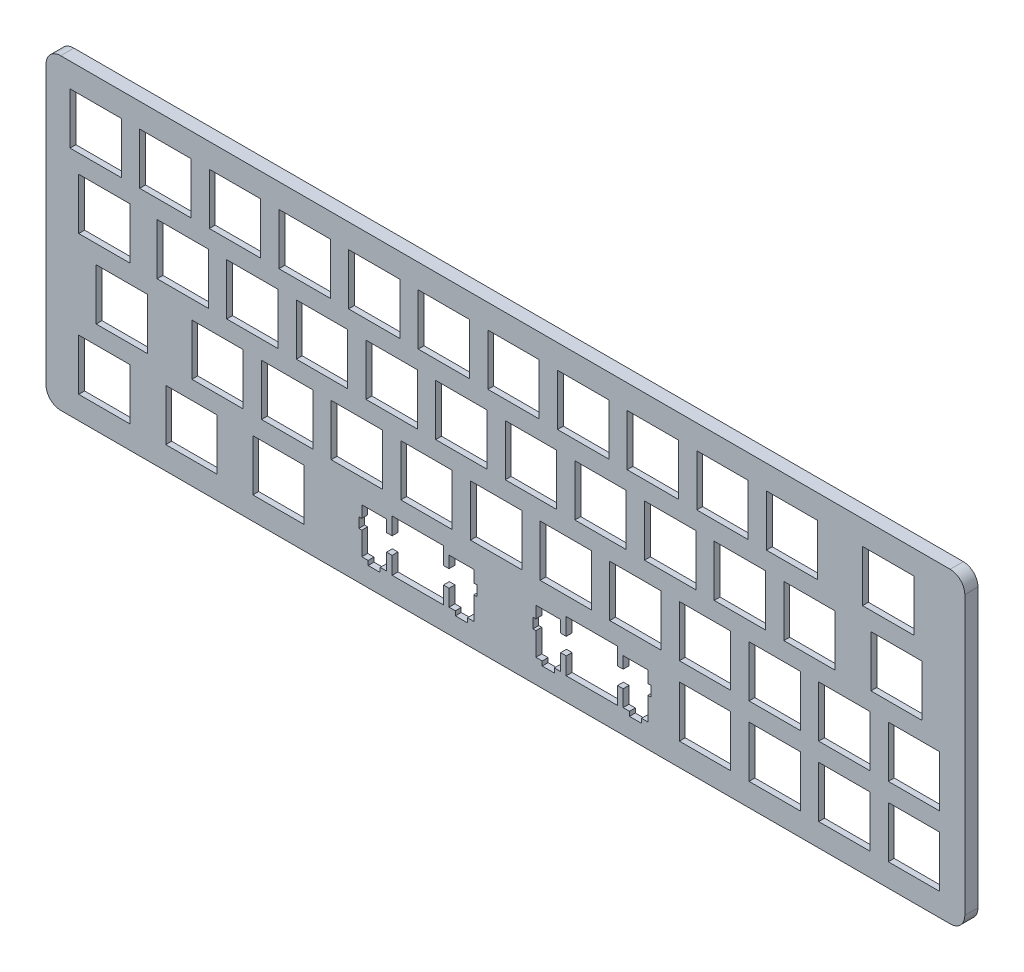
SolidWorks part; units mm, degrees
ref_plane "Front Plane" through (0, 0, 0) normal (0, 0, 1) x (1, 0, 0)
ref_plane "Top Plane" through (0, 0, 0) normal (0, 1, 0) x (1, 0, 0)
ref_plane "Right Plane" through (0, 0, 0) normal (1, 0, 0) x (0, 0, -1)
sketch "Sketch1" plane through (0, 0, 0) normal (0, 0, 1) x (1, 0, 0)
  line L0 (99.95, -108.45) -> (342.62, -108.45)
  line L1 (344.62, -110.45) -> (344.62, -186.25)
  line L2 (342.62, -188.25) -> (99.95, -188.25)
  line L3 (97.95, -186.25) -> (97.95, -110.45)
  line L4 (97.95, -110.45) -> (97.95, -186.25)
  line L5 (99.95, -106.45) -> (342.62, -106.45)
  line L6 (346.62, -110.45) -> (346.62, -186.25)
  line L7 (342.62, -190.25) -> (99.95, -190.25)
  line L8 (95.95, -110.45) -> (95.95, -186.25)
  circle A0 centre (147.5, -114.3) radius 1.1
  circle A1 centre (325.72, -114.3) radius 1.1
  circle A2 centre (332.75, -171.3) radius 1.1
  circle A3 centre (218.75, -152.3) radius 1.1138
  circle A4 centre (111.875, -171.3) radius 1.106
  arc A5 (342.62, -108.45) -> (344.62, -110.45) centre (342.62, -110.45) cw
  arc A6 (344.62, -186.25) -> (342.62, -188.25) centre (342.62, -186.25) cw
  arc A7 (99.95, -188.25) -> (97.95, -186.25) centre (99.95, -186.25) cw
  arc A8 (97.95, -110.45) -> (99.95, -108.45) centre (99.95, -110.45) cw
  arc A9 (95.95, -110.45) -> (99.95, -106.45) centre (99.95, -110.45) cw
  arc A10 (342.62, -106.45) -> (346.62, -110.45) centre (342.62, -110.45) cw
  arc A11 (346.62, -186.25) -> (342.62, -190.25) centre (342.62, -186.25) cw
  arc A12 (99.95, -190.25) -> (95.95, -186.25) centre (99.95, -186.25) cw
  dimension "D1" = 2
sketch "Sketch3" plane through (0, 0, 0) normal (0, 0, 1) x (1, 0, 0)
  line B0 (230.5, -113) -> (216.5, -113)
  line B1 (211.5, -127) -> (211.5, -113)
  line B2 (197.5, -113) -> (197.5, -127)
  line B3 (197.25, -132) -> (183.25, -132)
  line B4 (202.25, -146) -> (216.25, -146)
  line B5 (202.25, -132) -> (202.25, -146)
  line B6 (287.75, -170) -> (287.75, -184)
  line B7 (268.75, -165) -> (282.75, -165)
  line B8 (268.75, -151) -> (268.75, -165)
  line B9 (263.75, -151) -> (249.75, -151)
  line B10 (282.75, -151) -> (268.75, -151)
  line B11 (297.25, -146) -> (311.25, -146)
  line B12 (321, -146) -> (335, -146)
  line B13 (297.25, -132) -> (297.25, -146)
  line B14 (292.25, -146) -> (292.25, -132)
  line B15 (278.25, -132) -> (278.25, -146)
  line B16 (273.25, -146) -> (273.25, -132)
  line B17 (259.25, -132) -> (259.25, -146)
  line B18 (254.25, -146) -> (254.25, -132)
  line B19 (240.25, -146) -> (254.25, -146)
  line B20 (235.25, -132) -> (221.25, -132)
  line B21 (221.25, -146) -> (235.25, -146)
  line B22 (230.75, -165) -> (244.75, -165)
  line B23 (251.875, -170) -> (237.875, -170)
  line B24 (237.875, -170) -> (237.875, -184)
  line B25 (244.75, -165) -> (244.75, -151)
  line B26 (244.75, -151) -> (230.75, -151)
  line B27 (235.25, -146) -> (235.25, -132)
  line B28 (235.5, -113) -> (235.5, -127)
  line B29 (320.75, -184) -> (320.75, -170)
  line B30 (320.75, -170) -> (306.75, -170)
  line B31 (263.75, -165) -> (263.75, -151)
  line B32 (249.75, -151) -> (249.75, -165)
  line B33 (230.75, -151) -> (230.75, -165)
  line B34 (225.75, -165) -> (225.75, -151)
  line B35 (192.75, -151) -> (192.75, -165)
  line B36 (173.75, -165) -> (187.75, -165)
  line B37 (154.75, -165) -> (168.75, -165)
  line B38 (135.75, -165) -> (149.75, -165)
  line B39 (109.625, -165) -> (123.625, -165)
  line B40 (190.375, -184) -> (204.375, -184)
  line B41 (204.375, -184) -> (204.375, -170)
  line B42 (211.75, -151) -> (211.75, -165)
  line B43 (225.75, -151) -> (211.75, -151)
  line B44 (183.25, -146) -> (197.25, -146)
  line B45 (164.25, -132) -> (164.25, -146)
  line B46 (159.25, -146) -> (159.25, -132)
  line B47 (145.25, -132) -> (145.25, -146)
  line B48 (140.25, -146) -> (140.25, -132)
  line B49 (140.25, -132) -> (126.25, -132)
  line B50 (121.5, -127) -> (135.5, -127)
  line B51 (135.5, -113) -> (121.5, -113)
  line B52 (149.75, -151) -> (135.75, -151)
  line B53 (126.25, -146) -> (140.25, -146)
  line B54 (126.25, -132) -> (126.25, -146)
  line B55 (249.5, -127) -> (249.5, -113)
  line B56 (268.5, -127) -> (268.5, -113)
  line B57 (287.5, -113) -> (273.5, -113)
  line B58 (292.5, -113) -> (292.5, -127)
  line B59 (306.5, -127) -> (306.5, -113)
  line B60 (318.72, -127) -> (332.72, -127)
  line B61 (311.25, -146) -> (311.25, -132)
  line B62 (221.25, -132) -> (221.25, -146)
  line B63 (216.25, -146) -> (216.25, -132)
  line B64 (183.25, -132) -> (183.25, -146)
  line B65 (178.25, -146) -> (178.25, -132)
  line B66 (164.25, -146) -> (178.25, -146)
  line B67 (145.25, -146) -> (159.25, -146)
  line B68 (168.75, -151) -> (154.75, -151)
  line B69 (187.75, -151) -> (173.75, -151)
  line B70 (206.75, -165) -> (206.75, -151)
  line B71 (211.75, -165) -> (225.75, -165)
  line B72 (173.75, -151) -> (173.75, -165)
  line B73 (168.75, -165) -> (168.75, -151)
  line B74 (149.75, -165) -> (149.75, -151)
  line B75 (135.75, -151) -> (135.75, -165)
  line B76 (159.25, -132) -> (145.25, -132)
  line B77 (178.5, -113) -> (178.5, -127)
  line B78 (192.5, -113) -> (178.5, -113)
  line B79 (142.625, -170) -> (128.625, -170)
  line B80 (118.875, -184) -> (118.875, -170)
  line B81 (104.875, -170) -> (104.875, -184)
  line B82 (118.875, -170) -> (104.875, -170)
  line B83 (204.375, -170) -> (190.375, -170)
  line B84 (166.375, -184) -> (166.375, -170)
  line B85 (166.375, -170) -> (152.375, -170)
  line B86 (128.625, -170) -> (128.625, -184)
  line B87 (154.75, -151) -> (154.75, -165)
  line B88 (116.5, -127) -> (116.5, -113)
  line B89 (211.5, -113) -> (197.5, -113)
  line B90 (197.5, -127) -> (211.5, -127)
  line B91 (216.25, -132) -> (202.25, -132)
  line B92 (206.75, -151) -> (192.75, -151)
  line B93 (187.75, -165) -> (187.75, -151)
  line B94 (282.75, -184) -> (282.75, -170)
  line B95 (282.75, -170) -> (268.75, -170)
  line B96 (249.75, -165) -> (263.75, -165)
  line B97 (292.25, -132) -> (278.25, -132)
  line B98 (311.25, -132) -> (297.25, -132)
  line B99 (135.5, -127) -> (135.5, -113)
  line B100 (140.5, -113) -> (140.5, -127)
  line B101 (140.5, -127) -> (154.5, -127)
  line B102 (102.5, -113) -> (102.5, -127)
  line B103 (102.5, -127) -> (116.5, -127)
  line B104 (121.5, -113) -> (121.5, -127)
  line B105 (154.5, -113) -> (140.5, -113)
  line B106 (306.75, -184) -> (320.75, -184)
  line B107 (306.75, -170) -> (306.75, -184)
  line B108 (301.75, -184) -> (301.75, -170)
  line B109 (99.95, -106.45) -> (342.62, -106.45)
  line B110 (154.5, -127) -> (154.5, -113)
  line B111 (173.5, -113) -> (159.5, -113)
  line B112 (95.95, -186.25) -> (95.95, -110.45)
  line B113 (346.62, -110.45) -> (346.62, -186.25)
  line B114 (342.62, -190.25) -> (99.95, -190.25)
  line B115 (116.5, -113) -> (102.5, -113)
  line B116 (159.5, -127) -> (173.5, -127)
  line B117 (173.5, -127) -> (173.5, -113)
  line B118 (159.5, -113) -> (159.5, -127)
  line B119 (178.5, -127) -> (192.5, -127)
  line B120 (192.5, -127) -> (192.5, -113)
  line B121 (216.5, -127) -> (230.5, -127)
  line B122 (230.5, -127) -> (230.5, -113)
  line B123 (216.5, -113) -> (216.5, -127)
  line B124 (235.5, -127) -> (249.5, -127)
  line B125 (249.5, -113) -> (235.5, -113)
  line B126 (254.5, -127) -> (268.5, -127)
  line B127 (268.5, -113) -> (254.5, -113)
  line B128 (254.5, -113) -> (254.5, -127)
  line B129 (273.5, -127) -> (287.5, -127)
  line B130 (287.5, -127) -> (287.5, -113)
  line B131 (273.5, -113) -> (273.5, -127)
  line B132 (292.5, -127) -> (306.5, -127)
  line B133 (306.5, -113) -> (292.5, -113)
  line B134 (332.72, -127) -> (332.72, -113)
  line B135 (332.72, -113) -> (318.72, -113)
  line B136 (318.72, -113) -> (318.72, -127)
  line B137 (104.875, -146) -> (118.875, -146)
  line B138 (118.875, -146) -> (118.875, -132)
  line B139 (118.875, -132) -> (104.875, -132)
  line B140 (104.875, -132) -> (104.875, -146)
  line B141 (178.25, -132) -> (164.25, -132)
  line B142 (197.25, -146) -> (197.25, -132)
  line B143 (254.25, -132) -> (240.25, -132)
  line B144 (240.25, -132) -> (240.25, -146)
  line B145 (259.25, -146) -> (273.25, -146)
  line B146 (273.25, -132) -> (259.25, -132)
  line B147 (278.25, -146) -> (292.25, -146)
  line B148 (335, -146) -> (335, -132)
  line B149 (335, -132) -> (321, -132)
  line B150 (321, -132) -> (321, -146)
  line B151 (123.625, -165) -> (123.625, -151)
  line B152 (123.625, -151) -> (109.625, -151)
  line B153 (109.625, -151) -> (109.625, -165)
  line B154 (192.75, -165) -> (206.75, -165)
  line B155 (282.75, -165) -> (282.75, -151)
  line B156 (287.75, -165) -> (301.75, -165)
  line B157 (301.75, -165) -> (301.75, -151)
  line B158 (301.75, -151) -> (287.75, -151)
  line B159 (287.75, -151) -> (287.75, -165)
  line B160 (306.75, -165) -> (320.75, -165)
  line B161 (320.75, -165) -> (320.75, -151)
  line B162 (320.75, -151) -> (306.75, -151)
  line B163 (306.75, -151) -> (306.75, -165)
  line B164 (325.75, -165) -> (339.75, -165)
  line B165 (339.75, -165) -> (339.75, -151)
  line B166 (339.75, -151) -> (325.75, -151)
  line B167 (325.75, -151) -> (325.75, -165)
  line B168 (104.875, -184) -> (118.875, -184)
  line B169 (128.625, -184) -> (142.625, -184)
  line B170 (142.625, -184) -> (142.625, -170)
  line B171 (152.375, -184) -> (166.375, -184)
  line B172 (152.375, -170) -> (152.375, -184)
  line B173 (190.375, -170) -> (190.375, -184)
  line B174 (237.875, -184) -> (251.875, -184)
  line B175 (251.875, -184) -> (251.875, -170)
  line B176 (268.75, -184) -> (282.75, -184)
  line B177 (268.75, -170) -> (268.75, -184)
  line B178 (287.75, -184) -> (301.75, -184)
  line B179 (301.75, -170) -> (287.75, -170)
  line B180 (325.75, -184) -> (339.75, -184)
  line B181 (339.75, -184) -> (339.75, -170)
  line B182 (339.75, -170) -> (325.75, -170)
  line B183 (325.75, -170) -> (325.75, -184)
  arc B184 (99.95, -106.45) -> (95.95, -110.45) centre (99.95, -110.45) ccw
  arc B185 (346.62, -110.45) -> (342.62, -106.45) centre (342.62, -110.45) ccw
  arc B186 (342.62, -190.25) -> (346.62, -186.25) centre (342.62, -186.25) ccw
  arc B187 (95.95, -186.25) -> (99.95, -190.25) centre (99.95, -186.25) ccw
  line B188 (205.9044, -183.7589) -> (205.9044, -179.2889)
  line B189 (207.6294, -183.7589) -> (205.9044, -183.7589)
  line B190 (207.6294, -184.9589) -> (207.6294, -183.7589)
  line B191 (210.9294, -184.9589) -> (207.6294, -184.9589)
  line B192 (210.9294, -183.7589) -> (210.9294, -184.9589)
  line B193 (212.6544, -183.7589) -> (210.9294, -183.7589)
  line B194 (212.6544, -177.4739) -> (212.6544, -183.7589)
  line B195 (213.4794, -177.4739) -> (212.6544, -177.4739)
  line B196 (213.4794, -174.6889) -> (213.4794, -177.4739)
  line B197 (212.6544, -174.6889) -> (213.4794, -174.6889)
  line B198 (212.6544, -171.4589) -> (212.6544, -174.6889)
  line B199 (205.9044, -171.4589) -> (212.6544, -171.4589)
  line B200 (205.9044, -174.6889) -> (205.9044, -171.4589)
  line B201 (204.3794, -174.6889) -> (205.9044, -174.6889)
  line B202 (204.3794, -169.9889) -> (204.3794, -174.6889)
  line B203 (204.3794, -169.9889) -> (190.3794, -169.9889)
  line B204 (190.3794, -174.6889) -> (188.8544, -174.6889)
  line B205 (188.8544, -174.6889) -> (188.8544, -171.4589)
  line B206 (188.8544, -171.4589) -> (182.1044, -171.4589)
  line B207 (182.1044, -171.4589) -> (182.1044, -174.6889)
  line B208 (182.1044, -174.6889) -> (181.2794, -174.6889)
  line B209 (205.9044, -179.2889) -> (204.3794, -179.2889)
  line B210 (187.1294, -183.7589) -> (188.8544, -183.7589)
  line B211 (188.8544, -183.7589) -> (188.8544, -179.2889)
  line B212 (188.8544, -179.2889) -> (190.3794, -179.2889)
  line B213 (190.3794, -179.2889) -> (190.3794, -183.9889)
  line B214 (181.2794, -174.6889) -> (181.2794, -177.4739)
  line B215 (181.2794, -177.4739) -> (182.1044, -177.4739)
  line B216 (182.1044, -177.4739) -> (182.1044, -183.7589)
  line B217 (182.1044, -183.7589) -> (183.8294, -183.7589)
  line B218 (183.8294, -183.7589) -> (183.8294, -184.9589)
  line B219 (183.8294, -184.9589) -> (187.1294, -184.9589)
  line B220 (187.1294, -184.9589) -> (187.1294, -183.7589)
  line B221 (204.3794, -179.2889) -> (204.3794, -183.9889)
  line B222 (190.3794, -169.9889) -> (190.3794, -174.6889)
  line B223 (204.3794, -183.9889) -> (190.3794, -183.9889)
  line B224 (253.4033, -183.7589) -> (253.4033, -179.2889)
  line B225 (255.1283, -183.7589) -> (253.4033, -183.7589)
  line B226 (255.1283, -184.9589) -> (255.1283, -183.7589)
  line B227 (258.4283, -184.9589) -> (255.1283, -184.9589)
  line B228 (258.4283, -183.7589) -> (258.4283, -184.9589)
  line B229 (260.1533, -183.7589) -> (258.4283, -183.7589)
  line B230 (260.1533, -177.4739) -> (260.1533, -183.7589)
  line B231 (260.9783, -177.4739) -> (260.1533, -177.4739)
  line B232 (260.9783, -174.6889) -> (260.9783, -177.4739)
  line B233 (260.1533, -174.6889) -> (260.9783, -174.6889)
  line B234 (260.1533, -171.4589) -> (260.1533, -174.6889)
  line B235 (253.4033, -171.4589) -> (260.1533, -171.4589)
  line B236 (253.4033, -174.6889) -> (253.4033, -171.4589)
  line B237 (251.8783, -174.6889) -> (253.4033, -174.6889)
  line B238 (251.8783, -169.9889) -> (251.8783, -174.6889)
  line B239 (251.8783, -169.9889) -> (237.8783, -169.9889)
  line B240 (237.8783, -174.6889) -> (236.3533, -174.6889)
  line B241 (236.3533, -174.6889) -> (236.3533, -171.4589)
  line B242 (236.3533, -171.4589) -> (229.6033, -171.4589)
  line B243 (229.6033, -171.4589) -> (229.6033, -174.6889)
  line B244 (229.6033, -174.6889) -> (228.7783, -174.6889)
  line B245 (253.4033, -179.2889) -> (251.8783, -179.2889)
  line B246 (234.6283, -183.7589) -> (236.3533, -183.7589)
  line B247 (236.3533, -183.7589) -> (236.3533, -179.2889)
  line B248 (236.3533, -179.2889) -> (237.8783, -179.2889)
  line B249 (237.8783, -179.2889) -> (237.8783, -183.9889)
  line B250 (228.7783, -174.6889) -> (228.7783, -177.4739)
  line B251 (228.7783, -177.4739) -> (229.6033, -177.4739)
  line B252 (229.6033, -177.4739) -> (229.6033, -183.7589)
  line B253 (229.6033, -183.7589) -> (231.3283, -183.7589)
  line B254 (231.3283, -183.7589) -> (231.3283, -184.9589)
  line B255 (231.3283, -184.9589) -> (234.6283, -184.9589)
  line B256 (234.6283, -184.9589) -> (234.6283, -183.7589)
  line B257 (251.8783, -179.2889) -> (251.8783, -183.9889)
  line B258 (237.8783, -169.9889) -> (237.8783, -174.6889)
  line B259 (251.8783, -183.9889) -> (237.8783, -183.9889)
sketch_block_instance "switch_plate (3)-1"
sketch_block "switch_plate (3)"
sketch_block_instance "platemountstabv2-1"
sketch_block "platemountstabv2"
sketch_block_instance "platemountstabv2-2"
extrude "Boss-Extrude1" add sketch "Sketch3" along normal blind 1.6 contours B112 B187 B114 B186 B113 B185 B109 B184 B102 B115 B88 B103 B104 B51 B99 B50 B100 B105 B110 B101 B118 B111 B117 B116 B77 B78 B120 B119 B2 B89 B1 B90 B123 B0 B122 B121 B28 B125 B55 B124 B128 B127 region at (220.5788, -148.6962, 0)
extrude "Boss-Extrude2" add sketch "Sketch1" against normal blind 2 contours A12 L7 A11 L6 A10 L5 A9 L8 L3 A8 L0 A5 L1 A6 L2 A7 region at (221.285, -106.7143, 0)
